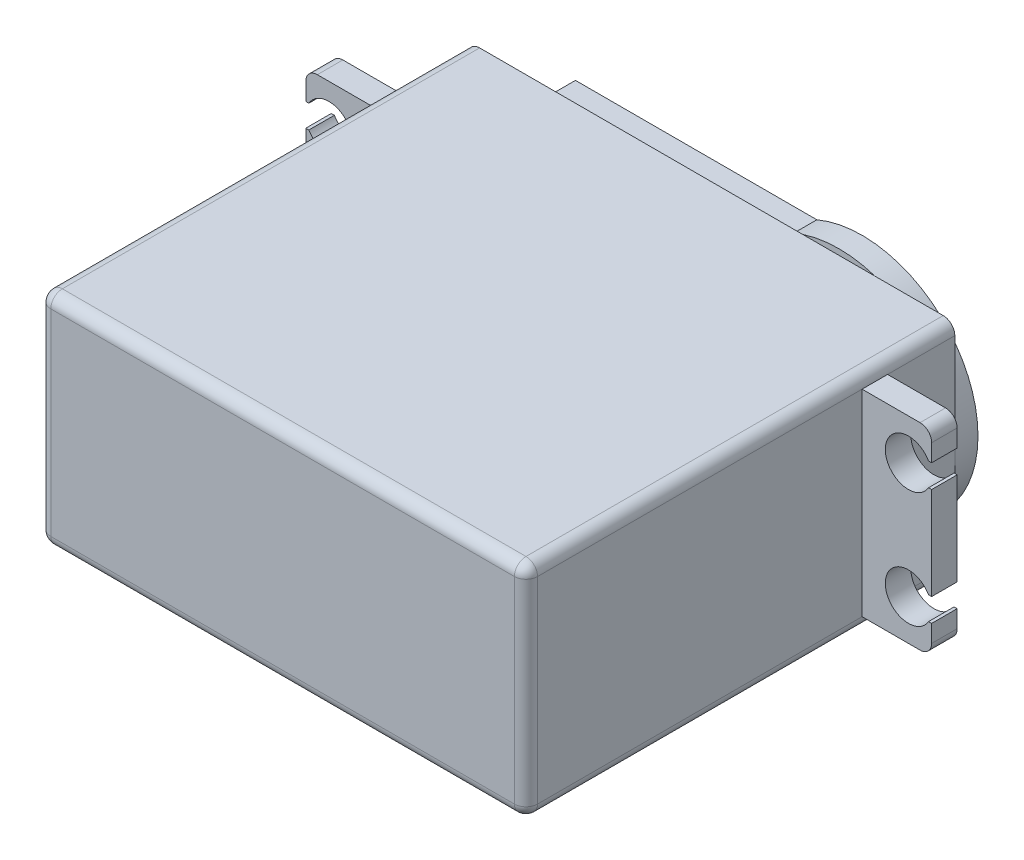
SolidWorks part; units mm, degrees
ref_plane "Front Plane" through (0, 0, 0) normal (0, 0, 1) x (1, 0, 0)
ref_plane "Top Plane" through (0, 0, 0) normal (0, 1, 0) x (1, 0, 0)
ref_plane "Right Plane" through (0, 0, 0) normal (1, 0, 0) x (0, 0, -1)
sketch "Sketch2" plane through (0, 0, 0) normal (0, 1, 0) x (1, 0, 0)
  line L1 (-31.0216, 21.9047) -> (10.9784, 21.9047)
  line L2 (-31.0216, 21.9047) -> (-31.0216, -15.0953)
  line L3 (-31.0216, -15.0953) -> (10.9784, -15.0953)
  line L4 (10.9784, 21.9047) -> (10.9784, -15.0953)
  dimension "D1" = 37
  dimension "D2" = 42
extrude "Boss-Extrude1" add sketch "Sketch2" along normal blind 19
fillet "Fillet1" radius 1 1 edges at (10.9784, 19, -3.4047)
fillet "Fillet2" radius 1 3 edges at (-31.0216, 19, -3.4047) (-31.0216, 0, -3.4047) (10.9784, 0, -3.4047)
sketch "Sketch3" plane through (10.9784, 0, 0) normal (1, 0, 0) x (0, 0, -1)
  line L0 (21.9047, 9.5) -> (13.9047, 9.5) construction
  line L1 (21.9047, 18) -> (21.9047, 1) construction
  line L2 (13.9047, 18) -> (13.9047, 1)
  line L3 (21.9047, 18) -> (-15.0953, 18) construction
  line L4 (-15.0953, 1) -> (21.9047, 1) construction
  line L5 (13.9047, 18) -> (16.1047, 18)
  line L6 (16.1047, 18) -> (16.1047, 1)
  line L7 (16.1047, 1) -> (13.9047, 1)
  line L8 (13.9047, 1) -> (13.9645, 0.9858)
  line M3 (-15.0953, 1) -> (21.9047, 1)
  line M5 (21.9047, 18) -> (-15.0953, 18)
  dimension "D1" = 8
  dimension "D2" = 2.2
extrude "Boss-Extrude2" add sketch "Sketch3" along normal blind 6 contours L6 L0 L2 M3 | L0 L6 L2 M5 region at (10.9784, 5.25, -15.0047) region at (10.9784, 13.75, -15.0047)
sketch "Sketch4" plane through (0, 0, -16.1047) normal (0, 0, -1) x (-1, 0, 0)
  line L0 (-16.9784, 9.5) -> (-10.9784, 9.5) construction
  line L1 (-16.9784, 18) -> (-16.9784, 1) construction
  line L2 (-10.9784, 18) -> (-10.9784, 1) construction
  line L4 (-16.9784, 9) -> (-10.9784, 9)
  line L5 (-16.9784, 9) -> (-16.9784, 10)
  line L6 (-16.9784, 10) -> (-10.9784, 10)
  line L7 (-10.9784, 9) -> (-10.9784, 10)
  line L8 (-16.9784, 9) -> (-10.9784, 10) construction
  line L9 (-16.9784, 10) -> (-10.9784, 9) construction
  point P6 (-13.9784, 9.5)
  dimension "D1" = 1
extrude "Boss-Extrude3" add sketch "Sketch4" along normal blind 1
chamfer "Chamfer1" distance 1 distance2 6 1 edges at (16.9784, 9.5, -17.1047) first distance on face at (16.9784, 9.5, -15.8047)
fillet "Fillet3" radius 1 2 edges at (16.9784, 18, -15.0047) (16.9784, 1, -15.0047)
sketch "Sketch5" plane through (0, 0, -16.1047) normal (0, 0, -1) x (-1, 0, 0)
  line L0 (-10.9784, 18) -> (-14.9784, 18) construction
  line L1 (-15.9784, 1) -> (-10.9784, 1) construction
  line L2 (-15.9784, 18) -> (-10.9784, 18) construction
  line L4 (-14.9784, 14.5) -> (-14.9784, 4.5) construction
  line L6 (-14.9784, 14.5) -> (-16.9784, 14.5) construction
  line L7 (-16.9784, 17) -> (-16.9784, 10) construction
  line L8 (-14.9784, 4.5) -> (-16.988, 4.5) construction
  line L9 (-16.9784, 15.5) -> (-16.9784, 13.5)
  line L10 (-16.9784, 3.5) -> (-16.9784, 5.5)
  line L11 (-16.9784, 15.5) -> (-16.7104, 15.5)
  line L12 (-16.9784, 3.5) -> (-16.7104, 3.5)
  line L13 (-16.9784, 13.5) -> (-16.7104, 13.5)
  line L14 (-16.9784, 5.5) -> (-16.7104, 5.5)
  arc A0 (-16.7104, 13.5) -> (-16.7104, 15.5) centre (-14.9784, 14.5) ccw
  arc A1 (-16.7104, 3.5) -> (-16.7104, 5.5) centre (-14.9784, 4.5) ccw
  point P22 (-16.9784, 14.5)
  dimension "D2" = 4
  dimension "D3" = 4
  dimension "D1" = 10
  dimension "D4" = 2
  dimension "D5" = 3.5
  dimension "D6" = 3.5
  dimension "D7" = 2
  dimension "D8" = 2
extrude "Cut-Extrude1" cut sketch "Sketch5" against normal blind 6
ref_plane "Plane5" through (-10.0216, 0, 0) normal (1, 0, 0) x (0, 0, -1)
mirror "Mirror9" about plane through (-10.0216, 0, 0) normal (1, 0, 0) of "Cut-Extrude1", "Fillet3", "Boss-Extrude3", "Boss-Extrude2"
chamfer "Chamfer2" distance 6 distance2 1 1 edges at (-37.0216, 9.5, -17.1047) first distance on face at (-34.0216, 9.5, -17.1047)
fillet "Fillet4" radius 1 8 edges at (-30.7287, 18.7071, 15.0953) (-31.0216, 9.5, 15.0953) (-30.7287, 0.2929, 15.0953) (-10.0216, 0, 15.0953) (10.6855, 0.2929, 15.0953) (10.9784, 9.5, 15.0953) (10.6855, 18.7071, 15.0953) (-10.0216, 19, 15.0953)
sketch "Sketch8" plane through (0, 0, -21.9047) normal (0, 0, -1) x (-1, 0, 0)
  line L0 (-10.9784, 9.5) -> (-0.9784, 9.5) construction
  line L1 (-10.9784, 9) -> (-10.9784, 10) construction
  line L2 (2.9241, 18.7071) -> (23.753, 18.7071)
  line L3 (2.9241, 0.2929) -> (23.753, 0.2929)
  line L4 (23.753, 18.7071) -> (23.753, 14.0234)
  line L5 (23.753, 4.9766) -> (23.753, 0.2929)
  arc A0 (2.9241, 18.7071) -> (2.9241, 0.2929) centre (-0.9784, 9.5) ccw
  arc A1 (23.753, 4.9766) -> (23.753, 14.0234) centre (19.8359, 9.5) ccw
  dimension "D2" = 20
  dimension "D1" = 10
extrude "Boss-Extrude4" add sketch "Sketch8" along normal blind 2
sketch "Sketch9" plane through (0, 0, -23.9047) normal (0, 0, -1) x (-1, 0, 0)
  circle A0 centre (-0.9784, 9.5) radius 6.5744
extrude "Boss-Extrude5" add sketch "Sketch9" along normal blind 1
sketch "Sketch10" plane through (0, 0, -24.9047) normal (0, 0, -1) x (-1, 0, 0)
  circle A0 centre (-0.9784, 9.5) radius 5.6897
extrude "Boss-Extrude6" add sketch "Sketch10" along normal blind 0.7
sketch "Sketch11" plane through (0, 0, -25.6047) normal (0, 0, -1) x (-1, 0, 0)
  circle A0 centre (-0.9784, 9.5) radius 1.55
  circle A1 centre (-0.9784, 9.5) radius 5.6897 construction
  dimension "D1" = 3.1
extrude "Cut-Extrude2" cut sketch "Sketch11" against normal blind 10 contours A0
